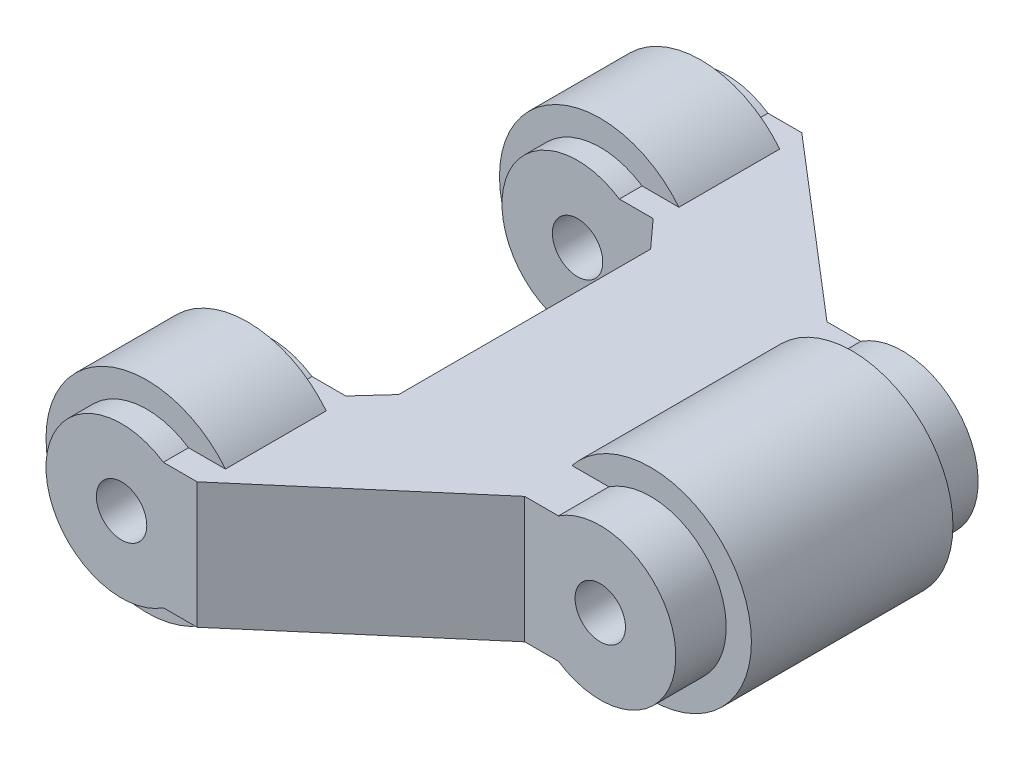
SolidWorks part; units mm, degrees
ref_plane "Спереди" through (0, 0, 0) normal (0, 0, 1) x (1, 0, 0)
ref_plane "Сверху" through (0, 0, 0) normal (0, 1, 0) x (1, 0, 0)
ref_plane "Справа" through (0, 0, 0) normal (1, 0, 0) x (0, 0, -1)
sketch "Эскиз1" plane through (0, 0, 0) normal (0, 0, 1) x (1, 0, 0)
  line L0 (0, 6.8428) -> (0, -6.3335) construction
  line L3 (-18.7141, 0) -> (20.1145, 0) construction
  circle A0 centre (-6.5, 0) radius 3
  circle A1 centre (6.5, 0) radius 3
  circle A3 centre (6.5, 0) radius 4
  circle A4 centre (-6.5, 0) radius 1
  circle A5 centre (6.5, 0) radius 1
  dimension "D1" = 6
  dimension "D2" = 8
  dimension "D5" = 2
  dimension "D4" = 13
extrude "Бобышка-Вытянуть1" add sketch "Эскиз1" along normal mid plane 12 contours A1 A5 region at (3.5849, 0, 0)
extrude "Бобышка-Вытянуть2" add sketch "Эскиз1<4>" along normal mid plane 8 contours A3 A1 region at (2.6131, 0, 0)
sketch "Эскиз1<4>" plane through (0, 0, 0) normal (0, 0, 1) x (1, 0, 0) same geometry as "Эскиз1"
extrude "Бобышка-Вытянуть3" add sketch "Эскиз1<5>" along normal mid plane 24 separate body contours A0 A4 region at (-9.4151, 0, 0)
sketch "Эскиз1<5>" plane through (0, 0, 0) normal (0, 0, 1) x (1, 0, 0) same geometry as "Эскиз1"
ref_plane "Плоскость1" through (0, 0, 9) normal (0, 0, 1) x (1, 0, 0)
sketch "Эскиз2" plane through (0, 0, 9) normal (0, 0, 1) x (1, 0, 0)
  circle A1 centre (-6.5, 0) radius 4
  circle A4 centre (-6.5, 0) radius 3 construction
  circle A5 centre (-6.5, 0) radius 3
  dimension "D1" = 8
extrude "Бобышка-Вытянуть4" add sketch "Эскиз2" along normal mid plane 4
mirror "Зеркальное отражение1" about plane through (0, 0, 0) normal (0, 0, 1) of "Бобышка-Вытянуть4"
sketch "Эскиз3" plane through (0, 0, 0) normal (0, 1, 0) x (1, 0, 0)
  line L0 (-13.7421, 0) -> (15.3447, 0) construction
  line L1 (-9.5, 7) -> (-9.5, -7) construction
  line L2 (-9.5, 6.1) -> (-3.5, 6.1)
  line L3 (-9.5, 6.1) -> (-9.5, -6.1)
  line L4 (-9.5, -6.1) -> (-3.5, -6.1)
  line L5 (-3.5, 6.1) -> (-3.5, -6.1)
  line L6 (-3.5, -7) -> (-3.5, 7) construction
  dimension "D1" = 12.2
extrude "Вырез-Вытянуть1" cut sketch "Эскиз3" against normal through all both and the other way through all
sketch "Эскиз4" plane through (0, 0, 0) normal (0, 1, 0) x (1, 0, 0)
  line L0 (9.5, 6) -> (3.5, 6) construction
  line L1 (9.5, 6) -> (3.5, 6)
  line L3 (5.5, 6) -> (5.5, -6) construction
  line L4 (-5.5, -12) -> (-5.5, -6.1) construction
  line L5 (-5.5, -12) -> (-5.5, -6.1)
  line L6 (-3.5, -12) -> (3.5, -6)
  line L7 (-18.3896, 0) -> (15.2245, 0) construction
  line L8 (-3.5, 12) -> (3.5, 6)
  line L10 (-5.5, -12) -> (-5.5, 12)
  line L11 (-3.5, 12) -> (-9.5, 12) construction
  line L13 (-5.5, 12) -> (-3.5, 12)
  line L14 (-5.5, -12) -> (-3.5, -12)
  line L24 (5.5, 6) -> (5.5, -6)
  line L25 (3.5, 6) -> (5.5, 6)
  line L26 (3.5, -6) -> (5.5, -6)
  line L27 (-9.5, -12) -> (-3.5, -12) construction
  line L30 (-3.5, 6.1) -> (-2.5, 5)
  line L31 (-2.5, 5) -> (-2.5, -5)
  line L33 (-2.5, -5) -> (-3.5, -6.1)
  line L34 (-3.5, -6.1) -> (-9.5, -6.1) construction
  line L35 (-3.5, -7) -> (-3.5, -6.1) construction
  line L36 (-3.5, -6.1) -> (-5.5, -6.1)
  line L37 (-3.5, 6.1) -> (-5.5, 6.1)
  line L38 (-9.5, -12) -> (-3.5, -12)
  line L39 (-6.5, 12) -> (-6.5, -12) construction
  dimension "D1" = 8
  dimension "D2" = 10
extrude "Бобышка-Вытянуть7" add sketch "Эскиз4" along normal mid plane 5 contours L31 L7 L24 L25 L8 L13 L10 L37 L30 region at (-0.0844, 0, 0)
